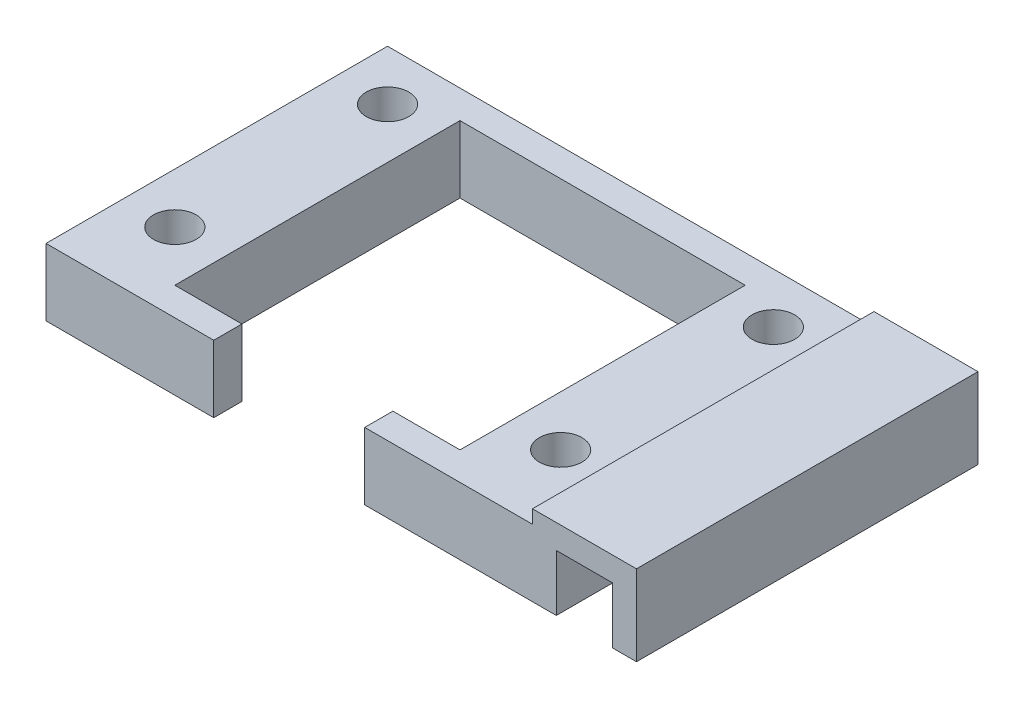
SolidWorks part; units mm, degrees
ref_plane "Front Plane" through (0, 0, 0) normal (0, 0, 1) x (1, 0, 0)
ref_plane "Top Plane" through (0, 0, 0) normal (0, 1, 0) x (1, 0, 0)
ref_plane "Right Plane" through (0, 0, 0) normal (1, 0, 0) x (0, 0, -1)
sketch "Sketch1" plane through (0, 0, 0) normal (0, 1, 0) x (1, 0, 0)
  line L1 (0, 0) -> (42.5, 0)
  line L2 (0, 0) -> (0, 42.5)
  line L3 (0, 42.5) -> (42.5, 42.5)
  line L4 (42.5, 0) -> (42.5, 42.5)
  line L5 (-15, 0) -> (57.5, 0)
  line L6 (-15, 0) -> (-15, 46.7)
  line L7 (-15, 46.7) -> (57.5, 46.7)
  line L8 (57.5, 0) -> (57.5, 46.7)
  line L9 (-15, 0) -> (10, 0)
  line L10 (-15, 0) -> (-15, -4.2)
  line L11 (-15, -4.2) -> (10, -4.2)
  line L12 (10, 0) -> (10, -4.2)
  line L13 (57.5, 0) -> (32.5, 0)
  line L14 (57.5, 0) -> (57.5, -4.2)
  line L15 (57.5, -4.2) -> (32.5, -4.2)
  line L16 (32.5, 0) -> (32.5, -4.2)
  circle A0 centre (-7.5, 7.5) radius 3.175
  circle A1 centre (-7.5, 39.2) radius 3.175
  circle A2 centre (50, 39.2) radius 3.175
  circle A3 centre (50, 7.5) radius 3.175
  dimension "D5" = 6.35
  dimension "D1" = 42.5
  dimension "D2" = 15
  dimension "D3" = 15
  dimension "D4" = 4.2
  dimension "D6" = 7.5
  dimension "D7" = 7.5
  dimension "D8" = 7.5
  dimension "D9" = 7.5
  dimension "D10" = 4.2
  dimension "D11" = 10
extrude "Boss-Extrude1" add sketch "Sketch1" along normal blind 10 contours L5 L8 L7 L6 L2 L3 L4 A3 A2 A1 A0 | L12 L1 L5 L10 L11 | L1 L16 L15 L14 L5 region at (-7.5, 0, -0.8624) region at (-2.5, 0, 2.1) region at (45, 0, 2.1)
sketch "Sketch4" plane through (53.3, 0, 4.2) normal (0, 0, -1) x (-1, 0, 0)
  line L0 (-7.75, 8.4) -> (-4.2, 8.4) construction
  line L1 (-19.7, 0) -> (-4.2, 0)
  line L2 (-19.7, 0) -> (-19.7, 12)
  line L3 (-19.7, 12) -> (-4.2, 12)
  line L4 (-4.2, 0) -> (-4.2, 12)
  line L5 (-16.15, 0) -> (-7.75, 0)
  line L6 (-16.15, 0) -> (-16.15, 8.4)
  line L7 (-16.15, 8.4) -> (-7.75, 8.4)
  line L8 (-7.75, 0) -> (-7.75, 8.4)
  line L9 (-16.15, 8.4) -> (-19.7, 8.4) construction
  point P9 (-21.0668, -0.3569)
  point P12 (-4.2, 0)
  line M16 (-4.2, 0) -> (-4.2, 10)
  dimension "D1" = 15.5
  dimension "D2" = 12
  dimension "D3" = 8.4
extrude "Boss-Extrude2" add sketch "Sketch4" along normal up to surface (50.9 mm away) contours L1 L8 L7 L6 L2 L3 L4 M16 region at (72.804, 6, 4.2) up to face at (21.25, 5, -46.7)
equation "\"8mm hole\" = 8.4mm"
equation "\"22mm hole\"= 23mm"
equation "\"15mm hole\"= 15.8mm"
equation "\"bed height offset\"= 3mm"
equation "\"motor width\"= 42.5mm"
equation "\"D3@Sketch4\"= \"8mm hole\""
